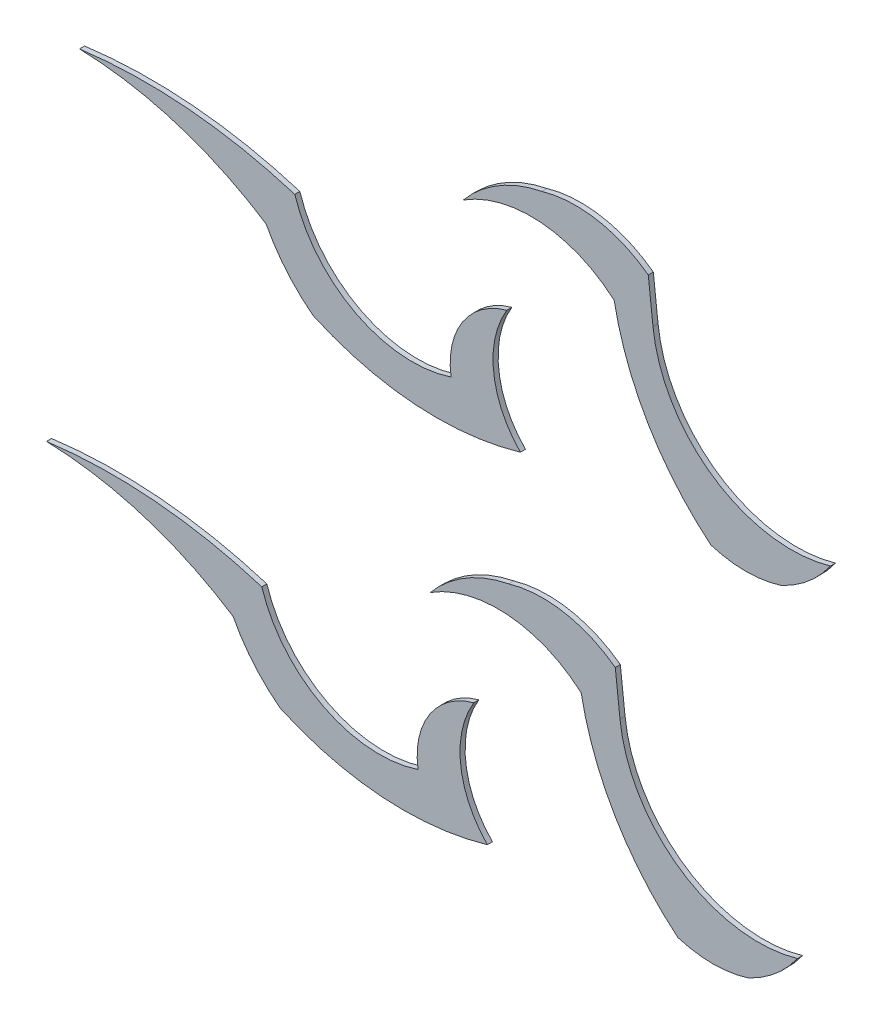
SolidWorks part; units mm, degrees
note: The reader was unsure of these and kept them because the rebuilt part matched: shared geometry of "스케치1<3>".
ref_plane "정면" through (0, 0, 0) normal (0, 0, 1) x (1, 0, 0)
ref_plane "윗면" through (0, 0, 0) normal (0, 1, 0) x (1, 0, 0)
ref_plane "우측면" through (0, 0, 0) normal (1, 0, 0) x (0, 0, -1)
sketch "스케치1" plane through (0, 0, 0) normal (0, 0, 1) x (1, 0, 0)
  line L0 (23.7442, 5.9969) -> (23.2538, 10.4103)
  line L1 (23.7045, 5.9925) -> (23.216, 10.3891)
  line L2 (20.4918, -29.1208) -> (20.0014, -24.7074)
  line L3 (20.4521, -29.1252) -> (19.9635, -24.7287)
  line L4 (23.2473, 5.9417) -> (22.7806, 10.1421)
  line L5 (23.2075, 5.9373) -> (22.7427, 10.1204)
  line L6 (19.9949, -29.176) -> (19.5282, -24.9757)
  line L7 (19.9551, -29.1805) -> (19.4903, -24.9974)
  arc A0 (23.7442, 5.9969) -> (41.9505, -4.7233) centre (36.8617, 7.4544) ccw
  arc A2 (28.6502, -10.3207) -> (36.0593, -10.3207) centre (32.3547, 1.1937) ccw
  arc A3 (36.0593, -10.3207) -> (41.9505, -4.7233) centre (30.5344, 1.3932) ccw
  arc A4 (18.8854, 5.9969) -> (2.1149, 4.6049) centre (11.1962, -3.0843) ccw
  arc A5 (23.2538, 10.4103) -> (12.127, 12.5377) centre (15.5951, 0.515) ccw
  arc A6 (12.127, 12.5377) -> (2.1149, 4.6049) centre (14.9066, -1.255) ccw
  arc A7 (10.0072, 0.9067) -> (11.1962, -11.5423) centre (16.8261, -4.7233) ccw
  arc A9 (10.0072, 0.9067) -> (2.7171, -7.9229) centre (10.777, -7.1531) ccw
  arc A10 (2.7171, -7.9229) -> (-11.6527, 0.0185) centre (-0.497, 3.2327) cw
  arc A11 (-11.6527, 0.0185) -> (-41.9505, 0.0185) centre (-26.8016, -47.8841) ccw
  arc A12 (-10.5598, -10.3207) -> (-15.3289, -4.7233) centre (-0.2058, 3.3316) cw
  arc A13 (-15.3289, -4.7233) -> (-41.9505, 0.0185) centre (-34.3035, -34.1497) ccw
  arc A14 (23.216, 10.3891) -> (12.1365, 12.4988) centre (15.5951, 0.515) ccw
  arc A15 (12.1365, 12.4988) -> (2.2742, 4.8495) centre (14.9066, -1.255) ccw
  arc A16 (18.9219, 6.0184) -> (2.2742, 4.8495) centre (11.1962, -3.0843) ccw
  arc A17 (28.6697, -10.2849) -> (18.9219, 6.0184) centre (46.5142, 11.4501) cw
  arc A18 (28.6697, -10.2849) -> (36.0446, -10.2834) centre (32.3547, 1.1937) ccw
  arc A19 (36.0446, -10.2834) -> (41.8618, -4.8032) centre (30.5344, 1.3932) ccw
  arc A20 (23.7045, 5.9925) -> (41.8618, -4.8032) centre (36.8617, 7.4544) ccw
  arc A21 (9.9151, 0.8571) -> (11.1149, -11.5267) centre (16.8261, -4.7233) ccw
  arc A22 (11.1149, -11.5267) -> (-10.5391, -10.2861) centre (1.8817, 16.9134) cw
  arc A23 (-10.5391, -10.2861) -> (-15.2985, -4.6953) centre (-0.2058, 3.3316) cw
  arc A24 (-15.2985, -4.6953) -> (-41.0891, 0.2408) centre (-34.3035, -34.1497) ccw
  arc A25 (-11.6852, -0.0131) -> (-41.0891, 0.2408) centre (-26.8016, -47.8841) ccw
  arc A26 (2.7602, -7.9521) -> (-11.6852, -0.0131) centre (-0.497, 3.2327) cw
  arc A27 (9.9151, 0.8571) -> (2.7602, -7.9521) centre (10.777, -7.1531) ccw
  arc A28 (20.4918, -29.1208) -> (38.6981, -39.8411) centre (33.6093, -27.6633) ccw
  arc A31 (32.8069, -45.4385) -> (38.6981, -39.8411) centre (27.282, -33.7246) ccw
  arc A32 (15.6329, -29.1208) -> (-1.1375, -30.5129) centre (7.9437, -38.2021) ccw
  arc A33 (20.0014, -24.7074) -> (8.8746, -22.58) centre (12.3427, -34.6027) ccw
  arc A34 (8.8746, -22.58) -> (-1.1375, -30.5129) centre (11.6542, -36.3728) ccw
  arc A35 (6.7548, -34.2111) -> (7.9437, -46.66) centre (13.5737, -39.8411) ccw
  arc A36 (7.9437, -46.66) -> (-13.8122, -45.4385) centre (-1.3707, -18.2044) cw
  arc A37 (6.7548, -34.2111) -> (-0.5353, -43.0407) centre (7.5245, -42.2709) ccw
  arc A38 (-0.5353, -43.0407) -> (-14.9051, -35.0992) centre (-3.7495, -31.885) cw
  arc A39 (-14.9051, -35.0992) -> (-45.203, -35.0992) centre (-30.054, -83.0019) ccw
  arc A40 (-13.8122, -45.4385) -> (-18.5813, -39.8411) centre (-3.4582, -31.7861) cw
  arc A41 (-18.5813, -39.8411) -> (-45.203, -35.0992) centre (-37.5559, -69.2675) ccw
  arc A42 (19.9635, -24.7287) -> (8.8841, -22.6189) centre (12.3427, -34.6027) ccw
  arc A43 (8.8841, -22.6189) -> (-0.9782, -30.2682) centre (11.6542, -36.3728) ccw
  arc A44 (15.6695, -29.0994) -> (-0.9782, -30.2682) centre (7.9437, -38.2021) ccw
  arc A45 (25.4173, -45.4027) -> (15.6695, -29.0994) centre (43.2618, -23.6676) cw
  arc A46 (25.4173, -45.4027) -> (32.7922, -45.4012) centre (29.1023, -33.924) ccw
  arc A47 (32.7922, -45.4012) -> (38.6094, -39.921) centre (27.282, -33.7246) ccw
  arc A48 (20.4521, -29.1252) -> (38.6094, -39.921) centre (33.6093, -27.6633) ccw
  arc A49 (6.6627, -34.2607) -> (7.8625, -46.6445) centre (13.5737, -39.8411) ccw
  arc A50 (7.8625, -46.6445) -> (-13.7915, -45.4039) centre (-1.3707, -18.2044) cw
  arc A51 (-13.7915, -45.4039) -> (-18.5509, -39.8131) centre (-3.4582, -31.7861) cw
  arc A52 (-18.5509, -39.8131) -> (-44.3415, -34.877) centre (-37.5559, -69.2675) ccw
  arc A53 (-14.9376, -35.1309) -> (-44.3415, -34.877) centre (-30.054, -83.0019) ccw
  arc A54 (-0.4922, -43.0699) -> (-14.9376, -35.1309) centre (-3.7495, -31.885) cw
  arc A55 (6.6627, -34.2607) -> (-0.4922, -43.0699) centre (7.5245, -42.2709) ccw
  arc A56 (22.7806, 10.1421) -> (12.2459, 12.0516) centre (15.5951, 0.515) ccw
  arc A57 (12.2459, 12.0516) -> (4.3188, 7.2329) centre (14.9066, -1.255) ccw
  arc A58 (19.3431, 6.2629) -> (4.3188, 7.2329) centre (11.1962, -3.0843) ccw
  arc A59 (28.8935, -9.8733) -> (19.3431, 6.2629) centre (46.5142, 11.4501) cw
  arc A60 (28.8935, -9.8733) -> (35.8753, -9.8546) centre (32.3547, 1.1937) ccw
  arc A61 (35.8753, -9.8546) -> (40.7896, -5.6686) centre (30.5344, 1.3932) ccw
  arc A62 (23.2473, 5.9417) -> (40.7896, -5.6686) centre (36.8617, 7.4544) ccw
  arc A63 (22.7427, 10.1204) -> (12.2554, 12.0127) centre (15.5951, 0.515) ccw
  arc A64 (12.2554, 12.0127) -> (4.5128, 7.4071) centre (14.9066, -1.255) ccw
  arc A65 (19.3798, 6.284) -> (4.5128, 7.4071) centre (11.1962, -3.0843) ccw
  arc A66 (28.9129, -9.8375) -> (19.3798, 6.284) centre (46.5142, 11.4501) cw
  arc A67 (28.9129, -9.8375) -> (35.8606, -9.8173) centre (32.3547, 1.1937) ccw
  arc A68 (35.8606, -9.8173) -> (40.6919, -5.7391) centre (30.5344, 1.3932) ccw
  arc A69 (23.2075, 5.9373) -> (40.6919, -5.7391) centre (36.8617, 7.4544) ccw
  arc A70 (19.5282, -24.9757) -> (8.9935, -23.0661) centre (12.3427, -34.6027) ccw
  arc A71 (8.9935, -23.0661) -> (1.0664, -27.8849) centre (11.6542, -36.3728) ccw
  arc A72 (16.0906, -28.8549) -> (1.0664, -27.8849) centre (7.9437, -38.2021) ccw
  arc A73 (25.6411, -44.9911) -> (16.0906, -28.8549) centre (43.2618, -23.6676) cw
  arc A74 (25.6411, -44.9911) -> (32.6229, -44.9724) centre (29.1023, -33.924) ccw
  arc A75 (32.6229, -44.9724) -> (37.5372, -40.7863) centre (27.282, -33.7246) ccw
  arc A76 (19.9949, -29.176) -> (37.5372, -40.7863) centre (33.6093, -27.6633) ccw
  arc A77 (19.4903, -24.9974) -> (9.003, -23.105) centre (12.3427, -34.6027) ccw
  arc A78 (9.003, -23.105) -> (1.2604, -27.7107) centre (11.6542, -36.3728) ccw
  arc A79 (16.1274, -28.8338) -> (1.2604, -27.7107) centre (7.9437, -38.2021) ccw
  arc A80 (25.6605, -44.9552) -> (16.1274, -28.8338) centre (43.2618, -23.6676) cw
  arc A81 (25.6605, -44.9552) -> (32.6082, -44.9351) centre (29.1023, -33.924) ccw
  arc A82 (32.6082, -44.9351) -> (37.4395, -40.8569) centre (27.282, -33.7246) ccw
  arc A83 (19.9551, -29.1805) -> (37.4395, -40.8569) centre (33.6093, -27.6633) ccw
  arc A84 (8.8889, 0.205) -> (10.2143, -11.3242) centre (16.8261, -4.7233) ccw
  arc A85 (10.2143, -11.3242) -> (-10.3015, -9.8889) centre (1.8817, 16.9134) cw
  arc A86 (-10.3015, -9.8889) -> (-14.9476, -4.3745) centre (-0.2058, 3.3316) cw
  arc A87 (-14.9476, -4.3745) -> (-33.8116, 1.3604) centre (-34.3035, -34.1497) ccw
  arc A88 (-12.0552, -0.3793) -> (-33.8116, 1.3604) centre (-26.8016, -47.8841) ccw
  arc A89 (3.2642, -8.2778) -> (-12.0552, -0.3793) centre (-0.497, 3.2327) cw
  arc A90 (8.8889, 0.205) -> (3.2642, -8.2778) centre (10.777, -7.1531) ccw
  arc A91 (8.8026, 0.1409) -> (10.1387, -11.3047) centre (16.8261, -4.7233) ccw
  arc A92 (10.1387, -11.3047) -> (-10.2808, -9.8544) centre (1.8817, 16.9134) cw
  arc A93 (-10.2808, -9.8544) -> (-14.917, -4.3467) centre (-0.2058, 3.3316) cw
  arc A94 (-14.917, -4.3467) -> (-33.3033, 1.3897) centre (-34.3035, -34.1497) ccw
  arc A95 (-12.0871, -0.4113) -> (-33.3033, 1.3897) centre (-26.8016, -47.8841) ccw
  arc A96 (3.3088, -8.3052) -> (-12.0871, -0.4113) centre (-0.497, 3.2327) cw
  arc A97 (8.8026, 0.1409) -> (3.3088, -8.3052) centre (10.777, -7.1531) ccw
  arc A98 (5.6365, -34.9128) -> (6.9619, -46.4419) centre (13.5737, -39.8411) ccw
  arc A99 (6.9619, -46.4419) -> (-13.5539, -45.0067) centre (-1.3707, -18.2044) cw
  arc A100 (-13.5539, -45.0067) -> (-18.2, -39.4923) centre (-3.4582, -31.7861) cw
  arc A101 (-18.2, -39.4923) -> (-37.064, -33.7574) centre (-37.5559, -69.2675) ccw
  arc A102 (-15.3077, -35.4971) -> (-37.064, -33.7574) centre (-30.054, -83.0019) ccw
  arc A103 (0.0118, -43.3956) -> (-15.3077, -35.4971) centre (-3.7495, -31.885) cw
  arc A104 (5.6365, -34.9128) -> (0.0118, -43.3956) centre (7.5245, -42.2709) ccw
  arc A105 (5.5502, -34.9769) -> (6.8863, -46.4225) centre (13.5737, -39.8411) ccw
  arc A106 (6.8863, -46.4225) -> (-13.5332, -44.9721) centre (-1.3707, -18.2044) cw
  arc A107 (-13.5332, -44.9721) -> (-18.1694, -39.4645) centre (-3.4582, -31.7861) cw
  arc A108 (-18.1694, -39.4645) -> (-36.5558, -33.728) centre (-37.5559, -69.2675) ccw
  arc A109 (-15.3396, -35.529) -> (-36.5558, -33.728) centre (-30.054, -83.0019) ccw
  arc A110 (0.0564, -43.423) -> (-15.3396, -35.529) centre (-3.7495, -31.885) cw
  arc A111 (5.5502, -34.9769) -> (0.0564, -43.423) centre (7.5245, -42.2709) ccw
  arc A112 (25.3978, -45.4385) -> (15.6329, -29.1208) centre (43.2618, -23.6676) cw construction
  arc A113 (25.3978, -45.4385) -> (32.8069, -45.4385) centre (29.1023, -33.924) ccw construction
  arc A114 (11.1962, -11.5423) -> (-10.5598, -10.3207) centre (1.8817, 16.9134) cw construction
  arc A115 (28.6502, -10.3207) -> (18.8854, 5.9969) centre (46.5142, 11.4501) cw construction
  dimension "D1" = 0.04
  dimension "D2" = 0.5
extrude "보스-돌출1" add sketch "스케치1" along normal blind 0.5 contours A91 A97 A96 A95 A94 A93 A92 | A69 L5 A63 A64 A65 A66 A67 A68
extrude "보스-돌출2" add sketch "스케치1<3>" along normal blind 0.5 separate body contours A83 L7 A77 A78 A79 A80 A81 A82 | A105 A111 A110 A109 A108 A107 A106
sketch "스케치1<3>" plane through (0, 0, 0) normal (0, 0, 1) x (1, 0, 0) same geometry as "스케치1"
